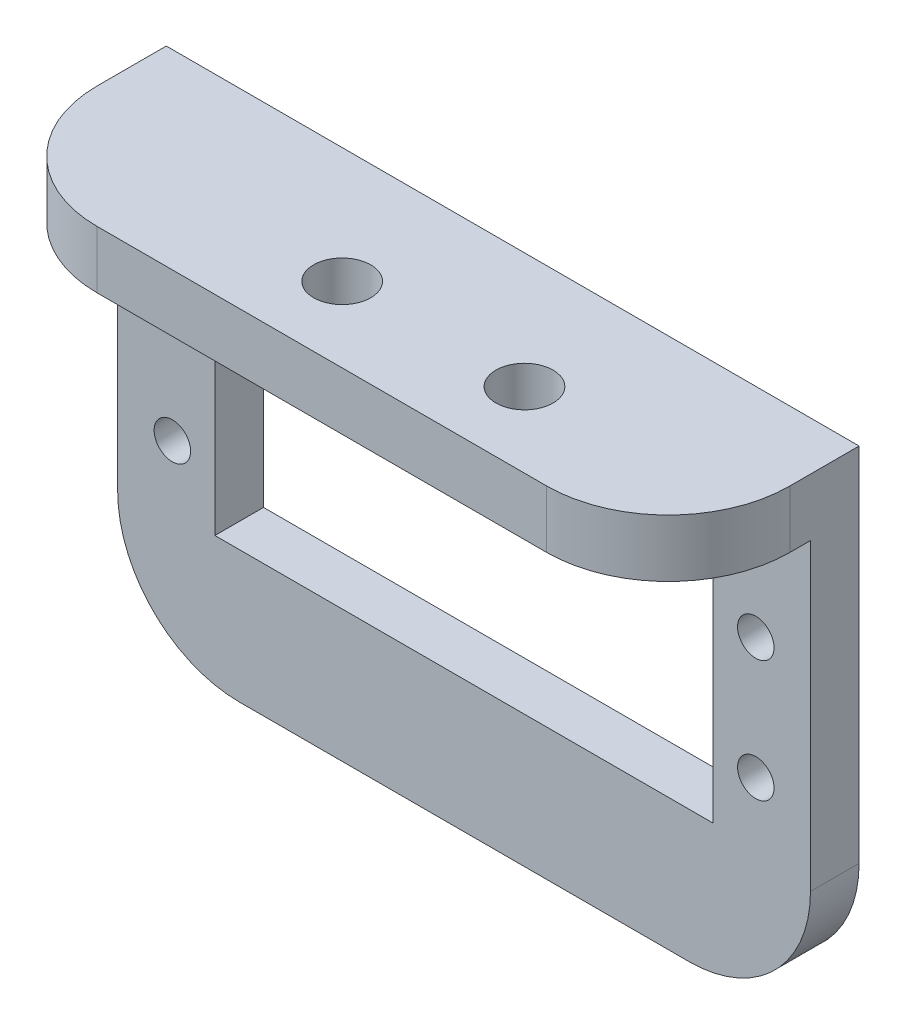
SolidWorks part; units mm, degrees
note: The reader was unsure of these and kept them because the rebuilt part matched: thickness of "Base-Flange2", "Edge-Flange1", "Sheet-Metal3", "Sheet-Metal4", "Sheet-Metal7", "Sheet-Metal9", "Sheet-Metal10"; flange length of "Edge-Flange1".
ref_plane "Front Plane" through (0, 0, 0) normal (0, 0, 1) x (1, 0, 0)
ref_plane "Top Plane" through (0, 0, 0) normal (0, 1, 0) x (1, 0, 0)
ref_plane "Right Plane" through (0, 0, 0) normal (1, 0, 0) x (0, 0, -1)
sketch "Sketch1" plane through (0, 0, 0) normal (0, 0, 1) x (1, 0, 0)
  line L0 (-6.3777, 0) -> (6.4702, 0) construction
  line L1 (-20.5, -10) -> (20.5, -10)
  line L2 (-20.5, -10) -> (-20.5, 10)
  line L3 (-20.5, 10) -> (20.5, 10)
  line L4 (20.5, -10) -> (20.5, 10)
  line L5 (-20.5, -10) -> (20.5, 10) construction
  line L6 (-20.5, 10) -> (20.5, -10) construction
  line L8 (0, -6.4239) -> (0, 6.4239) construction
  line L9 (-28.5, -20.86) -> (28.5, -20.86)
  line L10 (-28.5, -20.86) -> (-28.5, 14.14)
  line L11 (-28.5, 14.14) -> (28.5, 14.14)
  line L12 (28.5, -20.86) -> (28.5, 14.14)
  circle A0 centre (-24, 5) radius 1.5
  circle A1 centre (24, 5) radius 1.5
  circle A2 centre (24, -5) radius 1.5
  circle A3 centre (-24, -5) radius 1.5
  point P0 (0, 0)
  dimension "D3" = 3
  dimension "D1" = 41
  dimension "D2" = 20
  dimension "D4" = 24
  dimension "D5" = 5
  dimension "D6" = 0
  dimension "D7" = 57
  dimension "D8" = 35
  dimension "D9" = 28.5
  dimension "D10" = 14.14
base flange "Base-Flange2" sketch "Sketch1" thickness 4 reverse thickness direction no parameters "D1"=0.7366
edge flange "Edge-Flange1" sketch "Sketch14" flange angle 90 flange length 15.7 flange position bend outside bend radius 0.7366 thickness 4 relief rectangular parameters "D6"=10
sketch "Sketch14" plane through (0, 14.14, 0) normal (0, 1, 0) x (-1, 0, 0)
  line L0 (-28.5, 0) -> (28.5, 0) construction
  line L1 (-28.5, 0) -> (28.5, 0)
  line L2 (-28.5, 0) -> (-28.5, 11.7)
  line L3 (-28.5, 11.7) -> (28.5, 11.7)
  line L4 (28.5, 11.7) -> (28.5, 0)
  dimension "D1" = 11.7
bend "EdgeBend1" bend radius 0.7366 bend angle 90 parameters "D5"=1
sketch "Sketch15" plane through (0, 18.8766, 0) normal (0, 1, 0) x (1, 0, 0)
  line L1 (-28.5, -11.7) -> (28.5, -11.7) construction
  circle A0 centre (-31, -7.7) radius 1.6
  circle A1 centre (31, -7.7) radius 1.6
  point P2 (0, -11.7)
  dimension "D1" = 3.2
  dimension "D3" = 4
  dimension "D4" = 31
  dimension "D5" = 3.2
  dimension "D6" = 4
  dimension "D2" = 62
sketch "Sketch17" plane through (0, 18.8766, 0) normal (0, 1, 0) x (1, 0, 0)
  line L1 (28.5, -11.7) -> (-28.5, -11.7)
  line L2 (28.5, -11.7) -> (28.5, 4)
  line L3 (28.5, 4) -> (-28.5, 4)
  line L4 (-28.5, -11.7) -> (-28.5, 4)
fillet "Fillet1" radius 10 4 edges at (-28.5, 16.8766, 11.7) (28.5, 16.8766, 11.7) (-28.5, -20.86, -2) (28.5, -20.86, -2)
sketch "Sketch22" plane through (0, 18.8766, 0) normal (0, 1, 0) x (1, 0, 0)
  line L0 (-11.5, -9.696) -> (-11.5, -10.9812)
  line L5 (17.5, -9.696) -> (17.5, -10.9812)
  line L10 (17.5, -9.696) -> (17.5, 0.6534)
  line L15 (-9.5, -9.696) -> (15.5, -9.696)
  line L16 (-9.5, -9.696) -> (-9.5, -1.3466)
  line L17 (-9.5, -1.3466) -> (15.5, -1.3466)
  line L18 (15.5, -9.696) -> (15.5, -1.3466)
  line L19 (-9.5, -9.696) -> (15.5, -9.696)
  line L20 (-9.5, -9.696) -> (-9.5, -24.1929)
  line L21 (-9.5, -24.1929) -> (15.5, -24.1929)
  line L22 (15.5, -9.696) -> (15.5, -24.1929)
  line L23 (-11.5, 0.6534) -> (17.5, 0.6534)
  line L24 (-11.5, -9.696) -> (-11.5, 0.6534)
  line L25 (17.5, -10.9812) -> (15.5, -10.9812)
  line L26 (-11.5, -10.9812) -> (-9.5, -10.9812)
  line L27 (-1017.7726, -5.5213) -> (48982.2274, -5.5213) construction
  line L29 (-28.5, 4) -> (-28.5, -0.7366) construction
  line L33 (-1022.4989, 0.6534) -> (48977.5011, 0.6534) construction
  line L34 (-28.5, -0.7366) -> (28.5, -0.7366) construction
  circle A0 centre (3, -31.3466) radius 25
  circle A1 centre (-4.5, -5.5213) radius 2.35
  circle A2 centre (10.5, -5.5213) radius 2.35
  point P13 (-9.5, -5.5213)
  dimension "D2" = 50
  dimension "D7" = 4.7
  dimension "D1" = 2
  dimension "D3" = 30
  dimension "D4" = 25
  dimension "D5" = 17
  dimension "D6" = 5
  dimension "D8" = 5
  dimension "D9" = 14.497
  dimension "D10" = 1.39
extrude "Cut-Extrude4" cut sketch "Sketch22" against normal blind 10 contours L27 A1 A0 | A0 A1 | A1 L27 | A2 L27 | L27 A2 A0 | A0 A2 normal cut yes
extrude "Boss-Extrude1" add sketch "Sketch17" against normal up to vertex (4.7366 mm away) up to point (-28.5, 14.14, -4)
sketch "Sketch25" plane through (0, 18.8766, 0) normal (0, 1, 0) x (1, 0, 0)
  line L0 (-11.5, 1.9953) -> (-11.5, -10.9899)
  line L1 (17.5, 1.9953) -> (17.5, -10.9899)
  line L2 (17.5, 1.9953) -> (17.5, 12.3447)
  line L3 (-9.5, -9.7047) -> (15.5, -9.7047)
  line L4 (-9.5, -9.7047) -> (-9.5, -1.3553)
  line L5 (-9.5, -1.3553) -> (15.5, -1.3553)
  line L6 (15.5, -9.7047) -> (15.5, -1.3553)
  line L7 (-9.5, -9.7047) -> (15.5, -9.7047)
  line L8 (-9.5, -9.7047) -> (-9.5, -28.3553)
  line L9 (-9.5, -28.3553) -> (15.5, -28.3553)
  line L10 (15.5, -9.7047) -> (15.5, -28.3553)
  line L11 (-11.5, 12.3447) -> (17.5, 12.3447)
  line L12 (-11.5, 1.9953) -> (-11.5, 12.3447)
  line L13 (17.5, -10.9899) -> (15.5, -10.9899)
  line L14 (-11.5, -10.9899) -> (-9.5, -10.9899)
  line L15 (-1021.7281, -5.53) -> (48978.2719, -5.53) construction
  line L17 (-28.5, -11.7) -> (28.5, -11.7) construction
  circle A0 centre (3, -31.3553) radius 25
  circle A1 centre (-4.5, -5.53) radius 2.35
  circle A2 centre (10.5, -5.53) radius 2.35
  point P13 (-9.5, -5.53)
  point P23 (0, 0)
  point P27 (0, 0)
  point P28 (0, 0)
  point P31 (-31.9535, -19.3987)
  dimension "D1" = 50
  dimension "D11" = 4.7
  dimension "D2" = 18.6506
  dimension "D3" = 29
  dimension "D4" = 25
  dimension "D5" = 10.3494
  dimension "D6" = 6.17
  dimension "D7" = 8.3494
  dimension "D8" = 15
  dimension "D9" = 7
  dimension "D10" = 11
  dimension "D12" = 2
  dimension "D13" = 1.9953
extrude "Cut-Extrude5" cut sketch "Sketch25" against normal through all contours A1 L15 | L15 A1 A0 | L15 A2 A0 | A2 L15 | A0 A2 | A0 A1 normal cut yes
fillet "Fillet2" radius 10 2 edges at (-28.5, 16.5083, 11.7) (28.5, 16.5083, 11.7)
sketch "Bend-Lines3" [suppressed] plane through (0, 0, 0) normal (0, 1, 0) x (1, 0, 0)
sketch "Bounding-Box3" [suppressed] plane through (0, 0, 0) normal (0, 1, 0) x (1, 0, 0)
sheet metal parameters "Sheet-Metal3" thickness 4 parameters "D1"=0.7366
flat pattern "Flat-Pattern3" [suppressed]
sketch "Bend-Lines4" plane through (0, 0, 0) normal (0, 1, 0) x (1, 0, 0)
sketch3d "Bounding-Box4" [suppressed]
  line L0 (28.5, -23.15, 0) -> (-46.5, -23.15, 0) construction
  line L1 (28.5, 23.15, 0) -> (-46.5, 23.15, 0) construction
  line L2 (28.5, -23.15, 0) -> (28.5, 23.15, 0) construction
  line L3 (-46.5, -23.15, 0) -> (-46.5, 23.15, 0) construction
sheet metal parameters "Sheet-Metal4" thickness 4 parameters "D1"=0.7366, "D7"=6
flat pattern "Flat-Pattern3" [suppressed]
sketch "Bend-Lines4" plane through (0, 0, 0) normal (0, 0, 1) x (1, 0, 0)
  line L0 (28.5, 16.2893) -> (-28.5, 16.2893) construction
  line L1 (28.5, 16.2893) -> (-28.5, 16.2893) construction
sketch3d "Bounding-Box4" [suppressed]
  line L0 (-28.5, -20.86, 0) -> (28.5, -20.86, 0) construction
  line L1 (-28.5, 29.402, 0) -> (28.5, 29.402, 0) construction
  line L2 (-28.5, -20.86, 0) -> (-28.5, 29.402, 0) construction
  line L3 (28.5, -20.86, 0) -> (28.5, 29.402, 0) construction
bend of the flat pattern "Flatten-<EdgeBend1>1"
sketch "Sketch15-1" plane through (0, 17.702, -4) normal (0, 0, -1) x (1, 0, 0)
  line L1 (-18.5, -11.7) -> (18.5, -11.7) construction
  circle A0 centre (-31, -7.7) radius 1.6
  circle A1 centre (31, -7.7) radius 1.6
  dimension "D1" = 3.2
  dimension "D3" = 4
  dimension "D5" = 3.2
  dimension "D6" = 4
  dimension "D2" = 62
sheet metal parameters "Sheet-Metal7" thickness 4 parameters "D1"=0.7366, "D7"=6
flat pattern "Flat-Pattern3" [suppressed]
sketch "Bend-Lines4" plane through (0, 0, 0) normal (0, 0, 1) x (1, 0, 0)
sketch3d "Bounding-Box4" [suppressed]
  line L0 (-28.5, -20.86, 0) -> (28.5, -20.86, 0) construction
  line L1 (-28.5, 14.14, 0) -> (28.5, 14.14, 0) construction
  line L2 (-28.5, -20.86, 0) -> (-28.5, 14.14, 0) construction
  line L3 (28.5, -20.86, 0) -> (28.5, 14.14, 0) construction
bend of the flat pattern "Flatten-<EdgeBend1>1"
sketch "Sketch15-2" plane through (0, 18.8766, 0) normal (0, 1, 0) x (1, 0, 0)
  line L1 (-28.5, -11.7) -> (28.5, -11.7) construction
  circle A0 centre (-31, -7.7) radius 1.6
  circle A1 centre (31, -7.7) radius 1.6
  dimension "D1" = 3.2
  dimension "D3" = 4
  dimension "D5" = 3.2
  dimension "D6" = 4
  dimension "D2" = 62
sheet metal parameters "Sheet-Metal9" thickness 4 parameters "D1"=0.7366, "D7"=6
flat pattern "Flat-Pattern3" [suppressed]
sketch "Bend-Lines4" plane through (0, 0, 0) normal (0, 0, 1) x (1, 0, 0)
  line L0 (28.5, 16.2893) -> (-28.5, 16.2893) construction
  line L1 (28.5, 16.2893) -> (-28.5, 16.2893) construction
sketch3d "Bounding-Box4" [suppressed]
  line L0 (-28.5, -20.86, 0) -> (28.5, -20.86, 0) construction
  line L1 (-28.5, 29.402, 0) -> (28.5, 29.402, 0) construction
  line L2 (-28.5, -20.86, 0) -> (-28.5, 29.402, 0) construction
  line L3 (28.5, -20.86, 0) -> (28.5, 29.402, 0) construction
bend of the flat pattern "Flatten-<EdgeBend1>1"
sketch "Sketch15-1" plane through (0, 17.702, -4) normal (0, 0, -1) x (1, 0, 0)
  line L1 (-18.5, -11.7) -> (18.5, -11.7) construction
  circle A0 centre (-31, -7.7) radius 1.6
  circle A1 centre (31, -7.7) radius 1.6
  dimension "D1" = 3.2
  dimension "D3" = 4
  dimension "D5" = 3.2
  dimension "D6" = 4
  dimension "D2" = 62
sheet metal parameters "Sheet-Metal10" thickness 4 parameters "D1"=0.7366, "D7"=6
flat pattern "Flat-Pattern3" [suppressed]
sketch "Bend-Lines4" plane through (0, 0, 0) normal (0, 0, 1) x (1, 0, 0)
sketch3d "Bounding-Box4" [suppressed]
  line L0 (-28.5, -20.86, 0) -> (28.5, -20.86, 0) construction
  line L1 (-28.5, 14.14, 0) -> (28.5, 14.14, 0) construction
  line L2 (-28.5, -20.86, 0) -> (-28.5, 14.14, 0) construction
  line L3 (28.5, -20.86, 0) -> (28.5, 14.14, 0) construction
bend of the flat pattern "Flatten-<EdgeBend1>1"
sketch "Sketch15-2" plane through (0, 18.8766, 0) normal (0, 1, 0) x (1, 0, 0)
  line L1 (-18.5, -11.7) -> (18.5, -11.7) construction
  circle A0 centre (-31, -7.7) radius 1.6
  circle A1 centre (31, -7.7) radius 1.6
  dimension "D1" = 3.2
  dimension "D3" = 4
  dimension "D5" = 3.2
  dimension "D6" = 4
  dimension "D2" = 62
